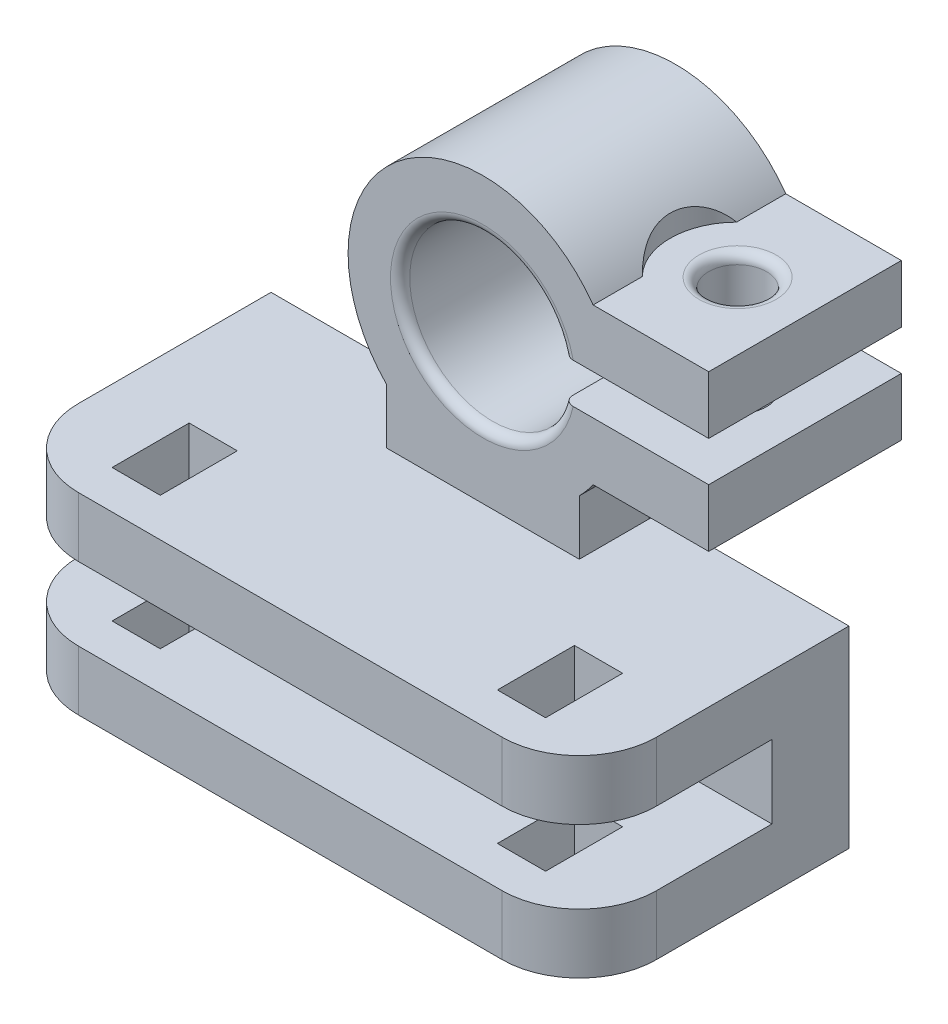
SolidWorks part; units mm, degrees
ref_plane "Plano frontal" through (0, 0, 0) normal (0, 0, 1) x (1, 0, 0)
ref_plane "Plano superior" through (0, 0, 0) normal (0, 1, 0) x (1, 0, 0)
ref_plane "Plano direito" through (0, 0, 0) normal (1, 0, 0) x (0, 0, -1)
sketch "Esboço1" plane through (0, 0, 0) normal (0, 0, 1) x (1, 0, 0)
  line L1 (-15, 5) -> (15, 5)
  line L2 (-15, 5) -> (-15, -5)
  line L3 (-15, -5) -> (15, -5)
  line L4 (15, 5) -> (15, -5)
  line L5 (-15, 5) -> (15, -5) construction
  line L6 (-15, -5) -> (15, 5) construction
  point P0 (0, 0)
  dimension "D1" = 10
  dimension "D2" = 30
extrude "Ressalto-extrusão1" add sketch "Esboço1" along normal blind 14
sketch "Esboço2" plane through (0, 0, 14) normal (0, 0, 1) x (1, 0, 0)
  line L0 (-15, 5) -> (-15, -5) construction
  line L1 (-15, 1.9) -> (15, 1.9)
  line L2 (-15, 1.9) -> (-15, -1.9)
  line L3 (-15, -1.9) -> (15, -1.9)
  line L4 (15, 1.9) -> (15, -1.9)
  line L5 (15, -5) -> (15, 5) construction
  line L6 (-15, 1.9) -> (15, -1.9) construction
  point P8 (0, 0)
  dimension "D1" = 3.8
extrude "Corte-extrusão1" cut sketch "Esboço2" against normal blind 10
fillet "Filete1" radius 4 4 edges at (-15, -3.45, 14) (15, 3.45, 14) (15, -3.45, 14) (-15, 3.45, 14)
sketch "Esboço3" plane through (0, 5, 0) normal (0, 1, 0) x (1, 0, 0)
  line L0 (0, 0) -> (0, -14) construction
  line L5 (11, -14) -> (-11, -14) construction
  line L6 (-10, -10) -> (10, -10) construction
  line L7 (-11.25, -8) -> (-8.75, -12) construction
  line L8 (11.25, -12) -> (8.75, -12)
  line L9 (11.25, -12) -> (11.25, -8)
  line L10 (11.25, -8) -> (8.75, -8)
  line L11 (8.75, -12) -> (8.75, -8)
  line L12 (11.25, -12) -> (8.75, -8) construction
  line L13 (11.25, -8) -> (8.75, -12) construction
  line L14 (-11.25, -12) -> (-8.75, -8) construction
  line L15 (-8.75, -12) -> (-8.75, -8)
  line L16 (-11.25, -8) -> (-8.75, -8)
  line L17 (-11.25, -12) -> (-11.25, -8)
  line L18 (-11.25, -12) -> (-8.75, -12)
  point P12 (0, -10)
  dimension "D1" = 4
  dimension "D2" = 4
  dimension "D3" = 2.5
  dimension "D4" = 20
extrude "Corte-extrusão2" cut sketch "Esboço3" against normal through all
sketch "Esboço4" plane through (0, 0, 0) normal (0, 0, -1) x (-1, 0, 0)
  line L0 (0, 0) -> (0, 1.75) construction
  line L1 (0, 12.75) -> (-7, 12.75) construction
  line L2 (-4.1726, 13.789) -> (-11.7172, 13.789)
  line L3 (-11.7172, 13.789) -> (-11.7172, 16.789)
  line L4 (-11.7172, 16.789) -> (-5.7172, 16.789)
  line L5 (-4.1726, 11.711) -> (-11.7172, 11.711)
  line L6 (-11.7172, 11.711) -> (-11.7172, 8.711)
  line L7 (-11.7172, 8.711) -> (-5.7172, 8.711)
  circle A0 centre (0, 12.75) radius 11 construction
  arc A1 (-4.1726, 11.711) -> (-4.1726, 13.789) centre (0, 12.75) ccw
  arc A2 (-5.7172, 8.711) -> (-5.7172, 16.789) centre (0, 12.75) ccw
  dimension "D1" = 22
  dimension "D3" = 8.6
  dimension "D4" = 14
  dimension "D2" = 1.75
  dimension "D5" = 6
  dimension "D6" = 3
extrude "Ressalto-extrusão2" add sketch "Esboço4" along normal blind 6 and the other way blind 4 separate body
sketch "Esboço5" plane through (0, 0, 4) normal (0, 0, -1) x (-1, 0, 0)
  line L0 (0, 12.75) -> (0, 0) construction
  line L1 (-5, 7.851) -> (5, 7.851)
  line L2 (-5, 7.851) -> (-5, 5)
  line L3 (-5, 5) -> (5, 5)
  line L4 (5, 7.851) -> (5, 5)
  line L6 (-15, 5) -> (15, 5) construction
  arc A0 (-5.7172, 8.711) -> (-5.7172, 16.789) centre (0, 12.75) ccw construction
  arc A1 (-4.1726, 11.711) -> (-4.1726, 13.789) centre (0, 12.75) ccw construction
  point P14 (0, 7.851)
  dimension "D1" = 10
extrude "Ressalto-extrusão3" add sketch "Esboço5" along normal blind 8
combine bodies "Combinar1" operation type add bodies to combine 105 103
chamfer "Chanfro1" distance 4 angle 68 1 edges at (0, 5, 0) first distance on face at (0, 5, -2)
sketch "Esboço7" plane through (0, 16.789, 0) normal (0, 1, 0) x (1, 0, 0)
  line L0 (5.7172, -4) -> (5.7172, 6) construction
  line L1 (11.7172, -4) -> (11.7172, 6) construction
  circle A0 centre (8.2172, 1) radius 1.5
  point P3 (8.2172, 1)
  point P6 (11.7172, 1)
  dimension "D1" = 2.5
  dimension "D2" = 3
extrude "Corte-extrusão3" cut sketch "Esboço7" against normal up to surface (8.078 mm away) up to face at (8.7172, 8.711, -1)
fillet "Filete2" radius 0.5 4 edges at (8.2172, 8.711, -2.5) (-4.3, 12.75, -6) (-4.3, 12.75, 4) (8.2172, 16.789, 0.5)
sketch "Esboço8" plane through (0, 16.789, 0) normal (0, 1, 0) x (1, 0, 0)
  circle A0 centre (8.2172, 1) radius 3.5
  dimension "D1" = 7
extrude "Corte-extrusão4" cut sketch "Esboço8" along normal blind 15
sketch "Esboço9" plane through (0, 8.711, 0) normal (0, -1, 0) x (1, 0, 0)
  circle A0 centre (8.2172, -1) radius 3.5
  dimension "D1" = 7
extrude "Corte-extrusão5" cut sketch "Esboço9" along normal blind 3.7
